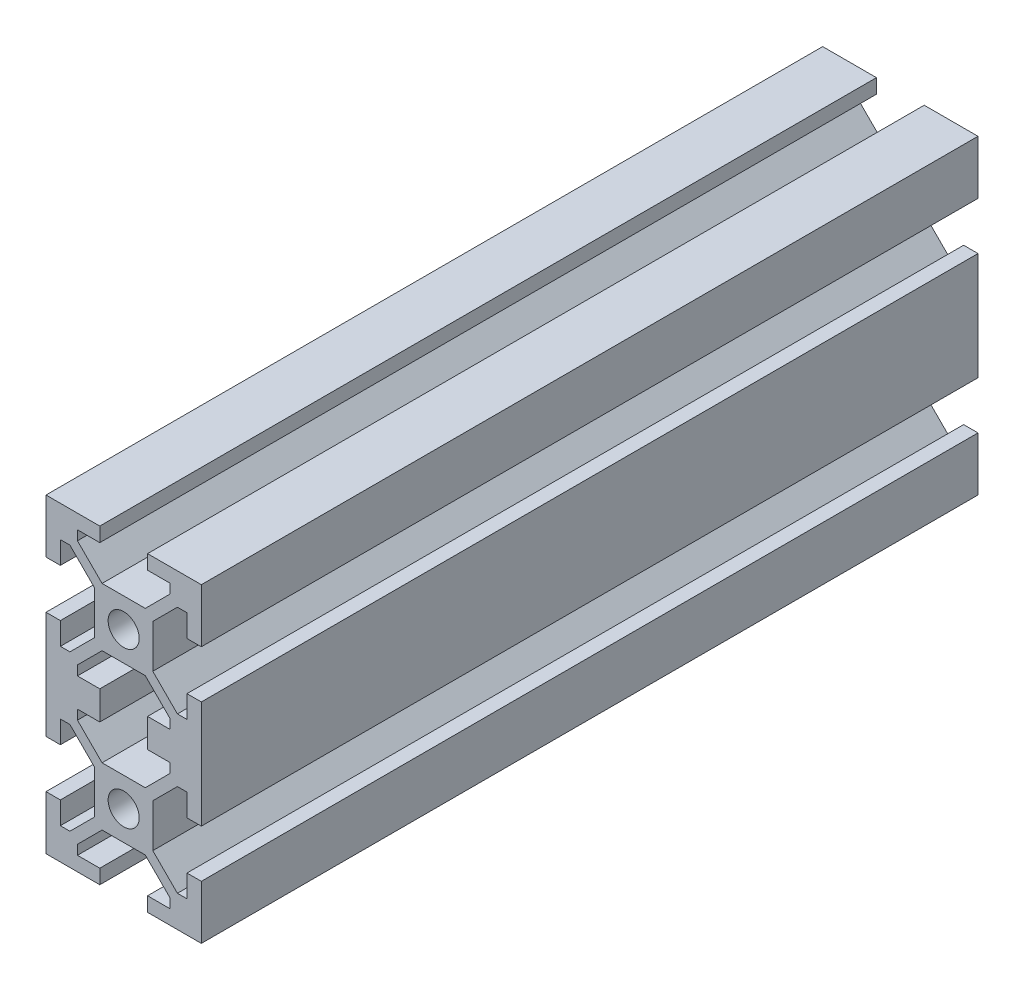
SolidWorks part; units mm, degrees
ref_plane "Front Plane" through (0, 0, 0) normal (0, 0, 1) x (1, 0, 0)
ref_plane "Top Plane" through (0, 0, 0) normal (0, 1, 0) x (1, 0, 0)
ref_plane "Right Plane" through (0, 0, 0) normal (1, 0, 0) x (0, 0, -1)
sketch "Sketch1" plane through (0, 0, 0) normal (0, 0, 1) x (1, 0, 0)
  line L0 (-10, 3.075) -> (-8.15, 3.075)
  line L1 (-10, 10) -> (10, 10) construction
  line L2 (-10, 10) -> (-10, -10) construction
  line L3 (-10, -10) -> (10, -10) construction
  line L4 (10, 10) -> (10, -10) construction
  line L5 (-10, 10) -> (10, -10) construction
  line L6 (-10, -10) -> (10, 10) construction
  line L7 (-8.15, 3.075) -> (-8.15, 5.95)
  line L8 (-8.15, 5.95) -> (-6.9187, 5.95)
  line L9 (-6.9187, 5.95) -> (-3.75, 2.7813)
  line L10 (-3.75, 2.7813) -> (-3.75, 0)
  line L11 (-3.75, 0) -> (-10, 0) construction
  line L12 (-10, 3.075) -> (-10, 10)
  line L13 (-2.7813, 3.75) -> (0, 3.75)
  line L14 (-5.95, 6.9187) -> (-2.7813, 3.75)
  line L15 (-5.95, 8.15) -> (-5.95, 6.9187)
  line L16 (-3.075, 8.15) -> (-5.95, 8.15)
  line L17 (-3.075, 10) -> (-3.075, 8.15)
  line L18 (-3.075, 10) -> (-10, 10)
  line L19 (2.7813, 3.75) -> (0, 3.75)
  line L20 (5.95, 6.9187) -> (2.7813, 3.75)
  line L21 (5.95, 8.15) -> (5.95, 6.9187)
  line L22 (3.075, 8.15) -> (5.95, 8.15)
  line L23 (3.075, 10) -> (3.075, 8.15)
  line L24 (3.075, 10) -> (10, 10)
  line L25 (10, 3.075) -> (10, 10)
  line L26 (10, 3.075) -> (8.15, 3.075)
  line L27 (8.15, 3.075) -> (8.15, 5.95)
  line L28 (8.15, 5.95) -> (6.9187, 5.95)
  line L29 (6.9187, 5.95) -> (3.75, 2.7813)
  line L30 (3.75, 2.7813) -> (3.75, 0)
  line L31 (3.75, -2.7813) -> (3.75, 0)
  line L32 (6.9187, -5.95) -> (3.75, -2.7813)
  line L33 (8.15, -5.95) -> (6.9187, -5.95)
  line L34 (8.15, -3.075) -> (8.15, -5.95)
  line L35 (10, -3.075) -> (8.15, -3.075)
  line L36 (10, -3.075) -> (10, -10)
  line L37 (3.075, -10) -> (10, -10)
  line L38 (3.075, -10) -> (3.075, -8.15)
  line L39 (3.075, -8.15) -> (5.95, -8.15)
  line L40 (5.95, -8.15) -> (5.95, -6.9187)
  line L41 (5.95, -6.9187) -> (2.7813, -3.75)
  line L42 (2.7813, -3.75) -> (0, -3.75)
  line L43 (-2.7813, -3.75) -> (0, -3.75)
  line L44 (-5.95, -6.9187) -> (-2.7813, -3.75)
  line L45 (-5.95, -8.15) -> (-5.95, -6.9187)
  line L46 (-3.075, -8.15) -> (-5.95, -8.15)
  line L47 (-3.075, -10) -> (-3.075, -8.15)
  line L48 (-3.075, -10) -> (-10, -10)
  line L49 (-10, -3.075) -> (-10, -10)
  line L50 (-10, -3.075) -> (-8.15, -3.075)
  line L51 (-8.15, -3.075) -> (-8.15, -5.95)
  line L52 (-8.15, -5.95) -> (-6.9187, -5.95)
  line L53 (-6.9187, -5.95) -> (-3.75, -2.7813)
  line L54 (-3.75, -2.7813) -> (-3.75, 0)
  circle A0 centre (0, 0) radius 2
  point P0 (0, 0)
  point P61 (0, 0)
  dimension "D7" = 4
  dimension "DX" = 20
  dimension "DY" = 20
  dimension "D1" = 6.15
  dimension "D2" = 1.85
  dimension "D3" = 1.37
  dimension "D4" = 4.05
  dimension "D5" = 3.75
  dimension "D6" = 4
extrude "Boss-Extrude1" add sketch "Sketch1" along normal blind 100
pattern_linear "LPattern1" count 2 spacing 20 along (0, 1, 0) of "Boss-Extrude1"
ref_plane "Plane1" through (0, 0, 50) normal (0, 0, 1) x (1, 0, 0)
ref_axis "Axis1" through (0, 0, 100) along (0, 0, -1)
equation "\"DY@Sketch1\"=\"DX@Sketch1\""
equation "\"D5@Sketch1\"=3.75*\"DX@Sketch1\"/20"
equation "\"D4@Sketch1\"=4.05*\"DX@Sketch1\"/20"
equation "\"D3@Sketch1\"=1.37*\"DX@Sketch1\"/20"
equation "\"D1@Sketch1\"=6.15*\"DX@Sketch1\"/20"
equation "\"D3@LPattern1\"=\"DX@Sketch1\""
equation "\"D4@LPattern1\"=\"DX@Sketch1\""
equation "\"D7@Sketch1\"=4*\"DX@Sketch1\"/20"
